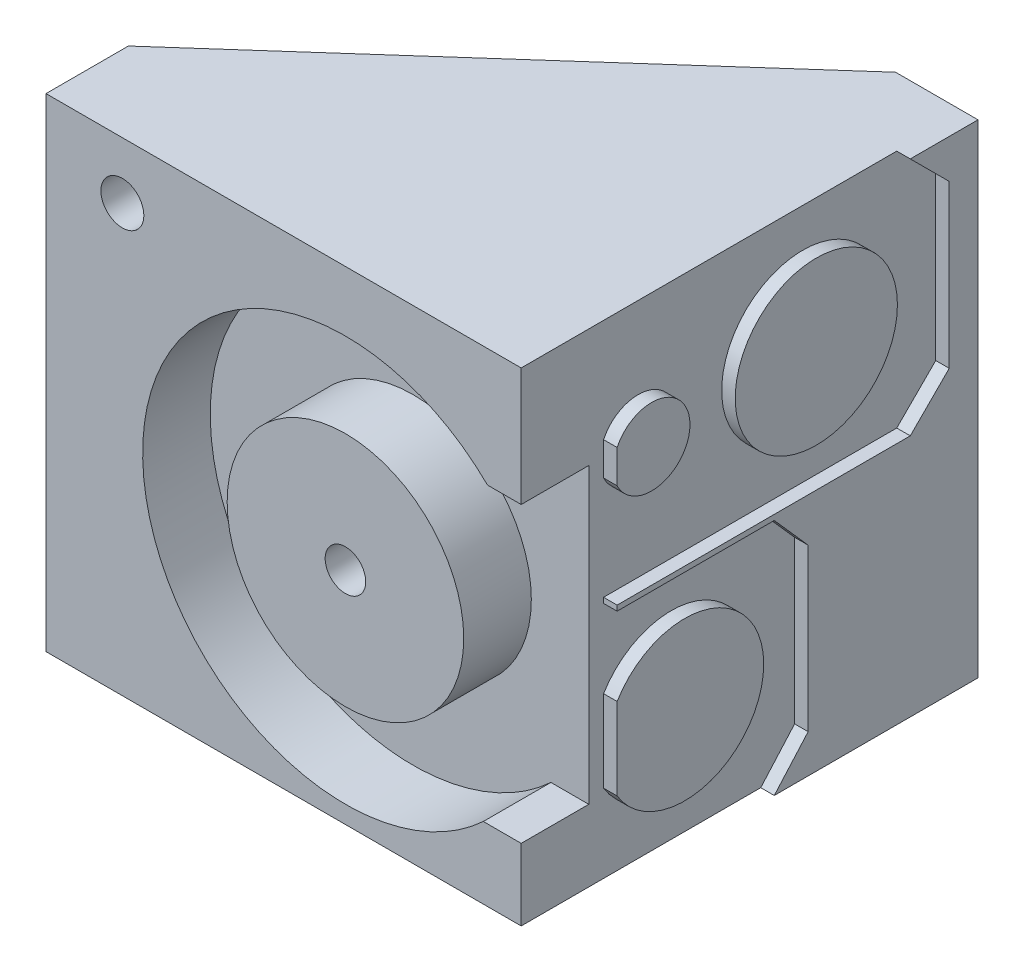
SolidWorks part; units mm, degrees
material "Aleación 1060"
ref_plane "Alzado" through (0, 0, 0) normal (0, 0, 1) x (1, 0, 0)
ref_plane "Planta" through (0, 0, 0) normal (0, 1, 0) x (1, 0, 0)
ref_plane "Vista lateral" through (0, 0, 0) normal (1, 0, 0) x (0, 0, -1)
sketch "Croquis1" plane through (0, 0, 0) normal (0, 1, 0) x (1, 0, 0)
  line L1 (-36.15, -32.79) -> (36.15, -32.79)
  line L2 (-36.15, -32.79) -> (-36.15, 32.79)
  line L3 (-36.15, 32.79) -> (36.15, 32.79)
  line L4 (36.15, -32.79) -> (36.15, 32.79)
  line L5 (-36.15, -32.79) -> (36.15, 32.79) construction
  line L6 (-36.15, 32.79) -> (36.15, -32.79) construction
  point P0 (0, 0)
  dimension "D1" = 72.3
  dimension "D2" = 65.58
extrude "Saliente-Extruir1" add sketch "Croquis1" along normal mid plane 71.5
sketch "Croquis2" plane through (36.15, 0, 0) normal (1, 0, 0) x (0, 0, -1)
  line L4 (-20.6, 35.75) -> (-32.79, 35.75)
  line L5 (-32.79, 35.75) -> (-32.79, -35.75)
  line L6 (-32.79, -35.75) -> (-20.6, -35.75)
  line L14 (-20.6, 35.75) -> (-20.6, -35.75)
  line L15 (-32.79, 35.75) -> (32.79, 35.75) construction
  line L16 (-32.79, -35.75) -> (32.79, -35.75) construction
  line L17 (-20.6, 35.75) -> (22.77, 35.75)
  line L18 (22.77, 35.75) -> (28.535, 29.985)
  line L19 (28.535, 29.985) -> (28.535, 6.035)
  line L20 (28.535, 6.035) -> (22.77, 0.27)
  line L21 (22.77, 0.27) -> (-20.6, 0.27)
  line L22 (-20.6, -0.51) -> (2.65, -0.51)
  line L23 (2.65, -0.51) -> (7.66, -6.18)
  line L24 (7.66, -6.18) -> (7.66, -30.08)
  line L25 (7.66, -30.08) -> (2.65, -35.75)
  line L26 (2.65, -35.75) -> (-20.6, -35.75)
  line L27 (32.79, 35.75) -> (32.79, -35.75) construction
  circle A3 centre (8.87, 18.01) radius 12
  arc A4 (-20.6, 15.553) -> (-20.6, 20.467) centre (-15.49, 18.01) ccw
  arc A5 (-20.6, -24.1844) -> (-20.6, -12.0756) centre (-10.6, -18.13) ccw
  line M19 (-32.79, -35.75) -> (32.79, -35.75)
  line M21 (32.79, 35.75) -> (-32.79, 35.75)
  line M22 (-32.79, 35.75) -> (-32.79, -35.75)
  dimension "D28" = 23.38
  dimension "D32" = 24
  dimension "D33" = 11.34
  dimension "D19" = 35.48
  dimension "D20" = 53.39
  dimension "D21" = 35.24
  dimension "D22" = 23.95
  dimension "D23" = 43.37
  dimension "D24" = 28.26
  dimension "D25" = 23.9
  dimension "D26" = 23.25
  dimension "D27" = 17.62
  dimension "D29" = 17.74
  dimension "D30" = 5.11
  dimension "D31" = 24.36
  dimension "D34" = 10
extrude "Cortar-Extruir1" cut sketch "Croquis2" against normal blind 2 contours L14 M21 M22 M19 | A4 L14 L21 L20 L19 L18 A3 M21 | A5 L14 L25 L24 L23 L22 M19 region at (36.15, 0, 26.695) region at (36.15, 35.1439, -1.085) region at (36.15, -29.9672, 20.1483)
sketch "Croquis3" plane through (0, 0, 32.79) normal (0, 0, 1) x (1, 0, 0)
  line L0 (34.15, 35.75) -> (-36.15, 32.3656)
  line L1 (-36.15, 32.3656) -> (-36.15, -32.7756)
  line L2 (-36.15, -32.7756) -> (34.15, -36.16)
  line L3 (34.15, -36.16) -> (34.15, 35.75)
  line L4 (34.15, -25.16) -> (28.5461, -25.16)
  line L5 (34.15, 18.25) -> (29.1646, 18.25)
  line L6 (34.15, -25.16) -> (34.15, 18.25)
  circle A0 centre (28.9, 30.2412) radius 3.5
  circle A1 centre (28.9, -30.6512) radius 3.5
  arc A2 (29.1646, 18.25) -> (28.5461, -25.16) centre (8.15, -3.16) ccw
  circle A3 centre (8.15, -3.16) radius 17.5
  circle A4 centre (8.15, -3.16) radius 3
  circle A5 centre (-24.8529, 27.3656) radius 3.175
  dimension "D4" = 7
  dimension "D9" = 6.35
  dimension "D10" = 6
  dimension "D11" = 35
  dimension "D12" = 60
  dimension "D1" = 70.3
  dimension "D2" = 71.91
  dimension "D3" = 65.1413
  dimension "D5" = 5.25
  dimension "D6" = 5.25
  dimension "D7" = 5.25
  dimension "D8" = 5.25
  dimension "D13" = 26
  dimension "D14" = 33
  dimension "D15" = 5
  dimension "D16" = 11.2971
  dimension "D17" = 11
  dimension "D18" = 17.5
extrude "Cortar-Extruir2" cut sketch "Croquis3" against normal blind 10 contours L5 A2 L4 L3 A3 | A4 region at (33.3293, -3.455, 32.79) region at (8.15, -3.16, 32.79)
sketch "Croquis4" plane through (0, 0, 0) normal (0, 1, 0) x (1, 0, 0)
  line L0 (-36.15, 32.79) -> (23.958, 32.79)
  line L1 (36.15, 32.79) -> (-36.15, 32.79) construction
  line L2 (23.958, 32.79) -> (-36.15, -20.6)
  line L3 (-36.15, 32.79) -> (-36.15, -32.79) construction
  line L4 (-36.15, -20.6) -> (-36.15, 32.79)
  dimension "D1" = 12.192
  dimension "D2" = 12.19
extrude "Cortar-Extruir3" cut sketch "Croquis4" against normal through all both and the other way through all
sketch "Croquis5" plane through (0, 0, 0) normal (0, 1, 0) x (1, 0, 0)
  line L0 (23.958, 32.79) -> (23.958, -20.6)
  line L1 (23.958, -20.6) -> (-36.15, -20.6)
  line L2 (-36.15, -20.6) -> (23.958, 32.79)
extrude "Cortar-Extruir4" cut sketch "Croquis5" against normal mid plane 62
extrude "Cortar-Extruir5" cut sketch "Croquis3<3>" against normal through all contours A5 region at (-24.8529, 27.3656, 32.79)
sketch "Croquis3<3>" plane through (0, 0, 32.79) normal (0, 0, 1) x (1, 0, 0) same geometry as "Croquis3"
